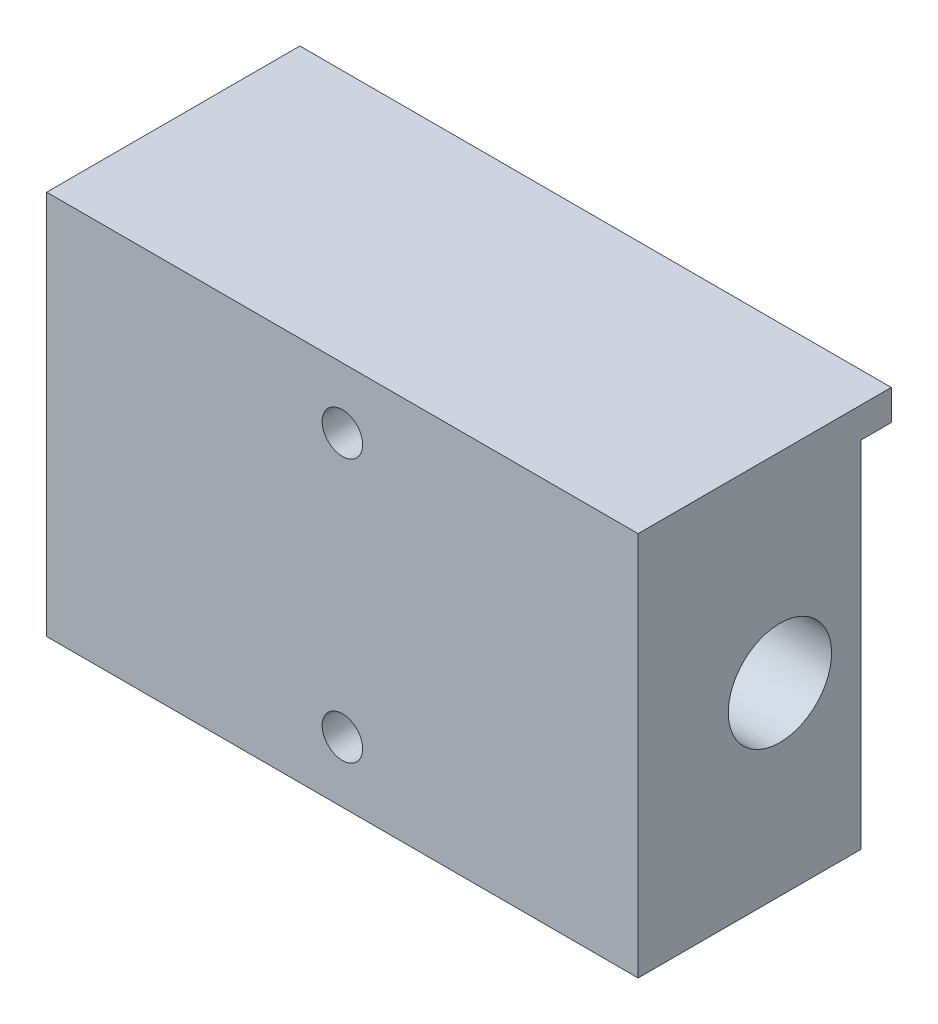
SolidWorks part; units mm, degrees
ref_plane "Alzado" through (0, 0, 0) normal (0, 0, 1) x (1, 0, 0)
ref_plane "Planta" through (0, 0, 0) normal (0, 1, 0) x (1, 0, 0)
ref_plane "Vista lateral" through (0, 0, 0) normal (1, 0, 0) x (0, 0, -1)
sketch "Croquis1" plane through (0, 0, 0) normal (0, 0, 1) x (1, 0, 0)
  line L1 (0, 0) -> (58.4, 0)
  line L2 (0, 0) -> (0, 38)
  line L3 (0, 38) -> (58.4, 38)
  line L4 (58.4, 0) -> (58.4, 38)
  dimension "D1" = 38
  dimension "D2" = 58.4
extrude "Saliente-Extruir1" add sketch "Croquis1" along normal blind 22
sketch "Croquis2" plane through (58.4, 0, 0) normal (1, 0, 0) x (0, 0, -1)
  circle A0 centre (-8, 18.2363) radius 5.1
  dimension "D1" = 10.2
  dimension "D2" = 8
extrude "Cortar-Extruir1" cut sketch "Croquis2" against normal through all
hole_wizard "Taladros de espiga de Ø4.0mm2" positions "Croquis4" profile "Croquis5" hole size "Ø4.0" standard "DIN"
sketch "Croquis4" plane through (0, 0, 22) normal (0, 0, 1) x (1, 0, 0)
  line L0 (0, 32) -> (58.4, 32) construction
  line L1 (0, 38) -> (0, 0) construction
  line L2 (58.4, 0) -> (58.4, 38) construction
  line L5 (58.4, 6) -> (0, 6) construction
  line L7 (58.4, 38) -> (0, 38) construction
  line L8 (29.2, 38) -> (29.2, 0) construction
  line L9 (0, 0) -> (58.4, 0) construction
  point P24 (29.2, 32)
  point P26 (29.2, 6)
  dimension "D1" = 6
  dimension "D2" = 6
sketch "Croquis5" plane through (29.2, 6, 22) normal (1, 0, 0) x (0, -1, 0)
  line L0 (0, 0) -> (0, 15.2017)
  line L1 (0, 15.2017) -> (2, 14)
  line L2 (2, 14) -> (2, 0)
  line L5 (2, 0) -> (0, 0)
  line L10 (0, 15.2017) -> (-2, 14) construction
  line L11 (0, -6.35) -> (0, 107.95) construction
  dimension "Diámetro de taladro" = 4
  dimension "Profundidad de taladro" = 14
  dimension "Ángulo de perforador" = 118
sketch "Croquis6" plane through (0, 0, 0) normal (0, 0, -1) x (-1, 0, 0)
  line L1 (-58.4, 35) -> (0, 35)
  line L2 (-58.4, 35) -> (-58.4, 38)
  line L3 (-58.4, 38) -> (0, 38)
  line L4 (0, 35) -> (0, 38)
  dimension "D1" = 3
extrude "Saliente-Extruir2" add sketch "Croquis6" along normal blind 3
hole_wizard "Perforador para roscar para macho de roscar para M33" positions "Croquis10" profile "Croquis11" hole size "M3" standard "DIN"
sketch "Croquis10" plane through (0, 0, 0) normal (-1, 0, 0) x (0, 0, 1)
  line L0 (8, 10.2363) -> (8, 26.2363) construction
  line L2 (16, 18.2363) -> (8, 18.2363) construction
  circle A0 centre (8, 18.2363) radius 8 construction
  point P5 (8, 10.2363)
  point P6 (8, 26.2363)
  point P8 (16, 18.2363)
  point P21 (8, 10.2363)
  dimension "D1" = 16
sketch "Croquis11" plane through (0, 18.2363, 16) normal (0, 1, 0) x (0, 0, 1)
  line L0 (0, 0) -> (0, 14.7511)
  line L1 (0, 14.7511) -> (1.25, 14)
  line L2 (1.25, 14) -> (1.25, 0)
  line L5 (1.25, 0) -> (0, 0)
  line L10 (0, 14.7511) -> (-1.25, 14) construction
  line L11 (0, -6.35) -> (0, 107.95) construction
  dimension "Diámetro de taladro" = 2.5
  dimension "Profundidad de taladro" = 14
  dimension "Ángulo de perforador" = 118
